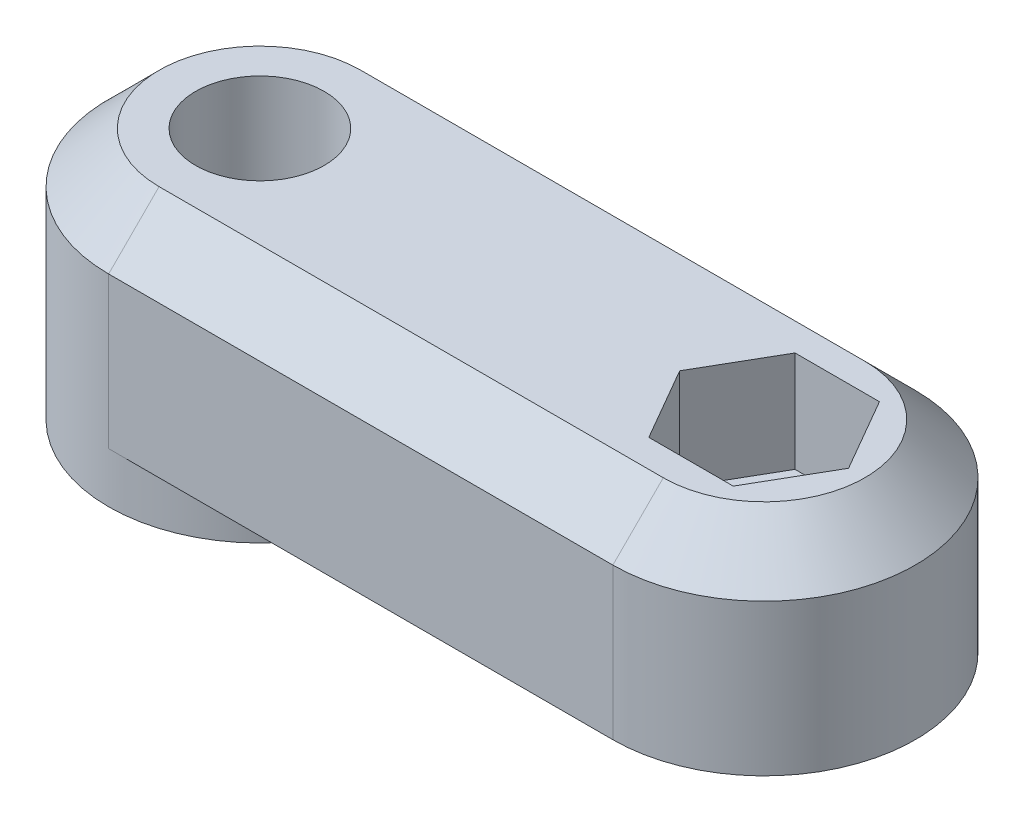
SolidWorks part; units mm, degrees
ref_plane "Front Plane" through (0, 0, 0) normal (0, 0, 1) x (1, 0, 0)
ref_plane "Top Plane" through (0, 0, 0) normal (0, 1, 0) x (1, 0, 0)
ref_plane "Right Plane" through (0, 0, 0) normal (1, 0, 0) x (0, 0, -1)
sketch "Sketch1" plane through (0, 0, 0) normal (0, 1, 0) x (1, 0, 0)
  line L0 (0, 0) -> (20, 0) construction
  line L1 (0, 6) -> (20, 6)
  line L2 (0, -6) -> (20, -6)
  arc A0 (0, 6) -> (0, -6) centre (0, 0) ccw
  arc A1 (20, -6) -> (20, 6) centre (20, 0) ccw
  point P3 (10, 0)
  dimension "D1" = 20
  dimension "D2" = 12
extrude "Boss-Extrude1" add sketch "Sketch1" along normal blind 10
sketch "Sketch2" plane through (0, 0, 0) normal (0, 0, 1) x (1, 0, 0)
  line L0 (0, 0) -> (0, 13.6635) construction
  line L1 (0, 10) -> (-2.55, 10)
  line L2 (0, 10) -> (-6, 10) construction
  line L3 (-2.55, 10) -> (-2.55, 5)
  line L4 (-2.55, 5) -> (-2.1, 5)
  line L5 (-2.1, 5) -> (-2.1, 2)
  line L6 (-2.1, 2) -> (-2.55, 2)
  line L7 (-2.55, 2) -> (-2.55, 0)
  line L8 (-2.55, 0) -> (0, 0)
  line L9 (0, 0) -> (0, 10)
  dimension "D1" = 5.1
  dimension "D2" = 4.2
  dimension "D3" = 5
  dimension "D4" = 3
revolve "Cut-Revolve1" cut sketch "Sketch2" angle 360 about L0
sketch "Sketch3" plane through (0, 0, 0) normal (0, 0, 1) x (1, 0, 0)
  line L0 (20, 0) -> (20, 13.4014) construction
  line L1 (20, 10) -> (17.5, 10)
  line L2 (0, 10) -> (20, 10) construction
  line L3 (17.5, 10) -> (17.5, 6)
  line L4 (17.5, 6) -> (17.925, 6)
  line L5 (17.925, 6) -> (17.925, 0)
  line L6 (0, 0) -> (20, 0) construction
  line L7 (17.925, 0) -> (20, 0)
  line L8 (20, 0) -> (20, 10)
  dimension "D1" = 4.15
  dimension "D2" = 5
  dimension "D3" = 6
revolve "Cut-Revolve2" cut sketch "Sketch3" angle 360 about L0
chamfer "Chamfer1" distance 2 angle 45 4 edges at (10, 10, 6) (26, 10, 0) (-6, 10, 0) (10, 10, -6)
sketch "Sketch4" plane through (0, 0, 0) normal (0, -1, 0) x (1, 0, 0)
  line L0 (0, 6) -> (20, 6) construction
  line L1 (2.1073, 3.65) -> (-2.1073, 3.65)
  line L2 (-2.1073, 3.65) -> (-4.2147, 0)
  line L3 (-4.2147, 0) -> (-2.1073, -3.65)
  line L4 (-2.1073, -3.65) -> (2.1073, -3.65)
  line L5 (2.1073, -3.65) -> (4.2147, 0)
  line L6 (4.2147, 0) -> (2.1073, 3.65)
  circle A0 centre (0, 0) radius 3.65 construction
  dimension "D1" = 7.3
extrude "Cut-Extrude1" cut sketch "Sketch4" against normal blind 5
sketch "Sketch5" plane through (0, 0, 0) normal (0, -1, 0) x (1, 0, 0)
  circle A0 centre (0, 0) radius 6
  circle A1 centre (0, 0) radius 34.2024
  arc A2 (20, -6) -> (20, 6) centre (20, 0) ccw construction
extrude "Cut-Extrude2" cut sketch "Sketch5" against normal blind 2
sketch "Sketch6" plane through (0, 10, 0) normal (0, 1, 0) x (1, 0, 0)
  line L0 (20, -6) -> (0, -6) construction
  line L1 (21.6743, -2.9) -> (23.3486, 0)
  line L2 (23.3486, 0) -> (21.6743, 2.9)
  line L3 (21.6743, 2.9) -> (18.3257, 2.9)
  line L4 (18.3257, 2.9) -> (16.6514, 0)
  line L5 (16.6514, 0) -> (18.3257, -2.9)
  line L6 (18.3257, -2.9) -> (21.6743, -2.9)
  circle A0 centre (20, 0) radius 2.9 construction
  dimension "D1" = 5.8
extrude "Cut-Extrude3" cut sketch "Sketch6" against normal blind 4
